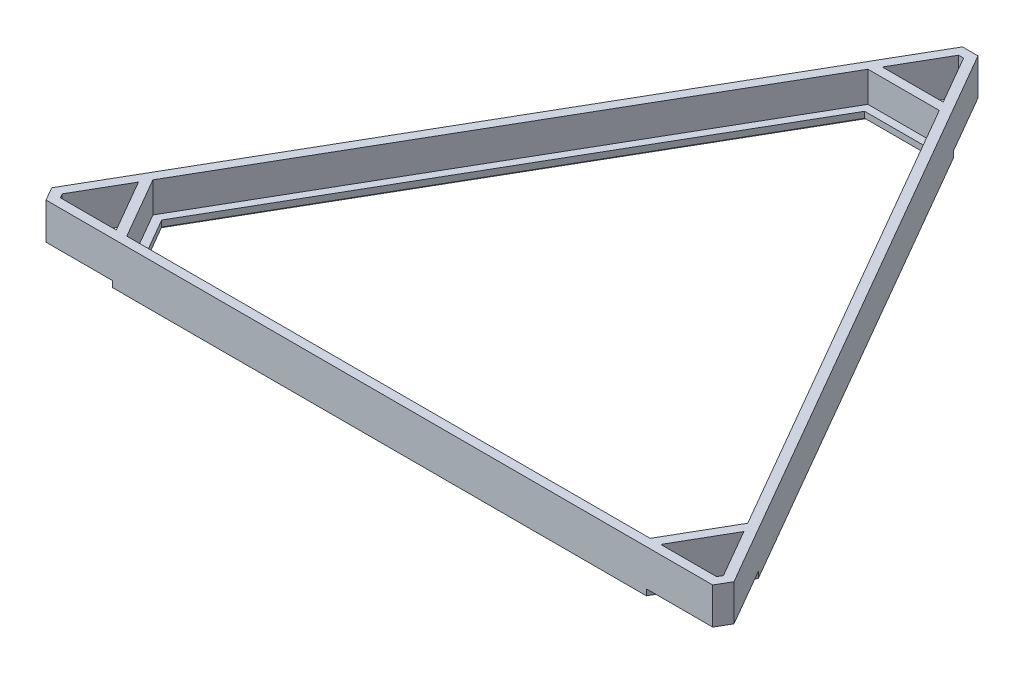
SolidWorks part; units mm, degrees
ref_plane "Front Plane" through (0, 0, 0) normal (0, 0, 1) x (1, 0, 0)
ref_plane "Top Plane" through (0, 0, 0) normal (0, 1, 0) x (1, 0, 0)
ref_plane "Right Plane" through (0, 0, 0) normal (1, 0, 0) x (0, 0, -1)
sketch "Sketch1" plane through (0, 0, 0) normal (0, 1, 0) x (1, 0, 0)
  line L17 (-4, 192.2576) -> (111, -6.9282) construction
  line L24 (4, 192.2576) -> (-111, -6.9282) construction
  line L25 (-115, 0) -> (115, 0) construction
  line L26 (0, -4.4282) -> (0, -1.4282) construction
  line L27 (-113, -3.4641) -> (-107, 0) construction
  line L28 (0, 192.2576) -> (0, 185.3294) construction
  line L29 (113, -3.4641) -> (107, 0) construction
  line L31 (-107.8246, -1.4282) -> (-108.6491, 0)
  line L39 (109.5566, -4.4282) -> (-109.5566, -4.4282)
  line L40 (-0.8246, 186.7576) -> (0.8246, 186.7576)
  line L41 (-109.5566, -4.4282) -> (-112.1132, 0)
  line L42 (-2.5566, 189.7576) -> (-112.1132, 0)
  line L43 (109.5566, -4.4282) -> (112.1132, 0)
  line L44 (-2.5566, 189.7576) -> (2.5566, 189.7576)
  line L45 (2.5566, 189.7576) -> (112.1132, 0)
  line L47 (108.6491, 0) -> (107.8246, -1.4282)
  line L50 (-99.4737, 15.8923) -> (-89.4737, -1.4282)
  line L51 (-107.8246, -1.4282) -> (-89.4737, -1.4282)
  line L52 (-99.4737, 15.8923) -> (-108.6491, 0)
  line L54 (89.4737, -1.4282) -> (107.8246, -1.4282)
  line L56 (89.4737, -1.4282) -> (99.4737, 15.8923)
  line L57 (99.4737, 15.8923) -> (108.6491, 0)
  line L58 (0, -1.4282) -> (0, 1.0718) construction
  line L59 (54.7369, 93.3788) -> (52.5718, 92.1288) construction
  line L62 (-10, 170.8653) -> (10, 170.8653)
  line L63 (-10, 170.8653) -> (-0.8246, 186.7576)
  line L64 (0.8246, 186.7576) -> (10, 170.8653)
  line L65 (94.4737, 7.2321) -> (91.8756, 8.7321) construction
  line L66 (-11.7321, 167.8653) -> (11.7321, 167.8653)
  line L67 (97.7417, 18.8923) -> (86.0096, -1.4282)
  line L68 (97.7417, 18.8923) -> (11.7321, 167.8653)
  line L69 (-54.7369, 93.3788) -> (-52.5718, 92.1288) construction
  line L70 (-84.5662, 1.0718) -> (84.5662, 1.0718)
  line L71 (-94.4737, 7.2321) -> (-91.8756, 8.7321) construction
  line L72 (-97.7417, 18.8923) -> (-86.0096, -1.4282)
  line L73 (-86.0096, -1.4282) -> (86.0096, -1.4282)
  line L74 (-97.7417, 18.8923) -> (-11.7321, 167.8653)
  line L75 (94.8549, 18.8923) -> (10.2887, 165.3653)
  line L76 (-10.2887, 165.3653) -> (-94.8549, 18.8923)
  line L77 (-91.8756, 8.7321) -> (-89.7106, 9.9821) construction
  line L78 (-94.8549, 18.8923) -> (-84.5662, 1.0718)
  line L79 (91.8756, 8.7321) -> (89.7106, 9.9821) construction
  line L80 (94.8549, 18.8923) -> (84.5662, 1.0718)
  line L81 (0, 167.8653) -> (0, 165.3653) construction
  line L82 (-10.2887, 165.3653) -> (10.2887, 165.3653)
  point P18 (0, -1.4282)
  point P41 (0, 167.8653)
  point P44 (91.8756, 8.7321)
  point P51 (-91.8756, 8.7321)
  point P55 (0, 1.0718)
  point P57 (-52.5718, 92.1288)
  point P61 (52.5718, 92.1288)
  point P65 (-89.7106, 9.9821)
  point P69 (89.7106, 9.9821)
  point P74 (0, 165.3653)
  dimension "D1" = 8
  dimension "D2" = 8
  dimension "D3" = 8
  dimension "D4" = 230
  dimension "D5" = 230
  dimension "D6" = 230
  dimension "D7" = 3
  dimension "D8" = 3
  dimension "D9" = 3
  dimension "D10" = 2.5
  dimension "D11" = 2.5
  dimension "D12" = 2.5
  dimension "D13" = 2.5
  dimension "D14" = 2.5
  dimension "D15" = 2.5
extrude "Boss-Extrude1" add sketch "Sketch1" along normal blind 12 contours L45 L43 L39 L41 L42 L44 | L74 L66 L68 L67 L73 L72 | L52 L31 L51 L50 | L57 L47 L54 L56 | L64 L62 L63 L40
extrude "Boss-Extrude2" add sketch "Sketch1<4>" along normal blind 2 contours L74 L72 L73 L67 L68 L66 L76 L82 L75 L80 L70 L78 region at (0, 0, -167.6067)
sketch "Sketch1<4>" plane through (0, 0, 0) normal (0, 1, 0) x (1, 0, 0) same geometry as "Sketch1"
sketch "Sketch2" plane through (0, 0, 0) normal (0, -1, 0) x (1, 0, 0)
  line L24 (-2.5566, -189.7576) -> (-112.1132, 0) construction
  line L25 (109.5566, 4.4282) -> (-109.5566, 4.4282) construction
  line L27 (2.5566, -189.7576) -> (112.1132, 0) construction
  line L33 (-89.4737, 1.4282) -> (-101.2058, -18.8923) construction
  line L34 (-89.4737, 1.4282) -> (-87.7417, 4.4282) construction
  line L35 (-11.7321, -167.8653) -> (11.7321, -167.8653)
  line L36 (89.4737, 1.4282) -> (87.7417, 4.4282) construction
  line L37 (99.4737, -15.8923) -> (101.2058, -18.8923) construction
  line L38 (86.0096, 1.4282) -> (97.7417, -18.8923)
  line L40 (101.2058, -18.8923) -> (87.7417, 4.4282)
  line L42 (-10, -170.8653) -> (-13.4641, -170.8653) construction
  line L43 (10, -170.8653) -> (13.4641, -170.8653) construction
  line L44 (87.7417, 4.4282) -> (-87.7417, 4.4282)
  line L45 (-97.7417, -18.8923) -> (-86.0096, 1.4282)
  line L46 (57.3349, -94.8788) -> (54.7369, -93.3788) construction
  line L47 (0, 4.4282) -> (0, 1.4282) construction
  line L48 (-87.7417, 4.4282) -> (-101.2058, -18.8923)
  line L49 (11.7321, -167.8653) -> (97.7417, -18.8923)
  line L50 (-86.0096, 1.4282) -> (86.0096, 1.4282)
  line L51 (-57.3349, -94.8788) -> (-54.7369, -93.3788) construction
  line L52 (-11.7321, -167.8653) -> (-97.7417, -18.8923)
  line L53 (-101.2058, -18.8923) -> (-13.4641, -170.8653)
  line L54 (-13.4641, -170.8653) -> (13.4641, -170.8653)
  line L55 (13.4641, -170.8653) -> (101.2058, -18.8923)
  point P66 (0, -167.8653)
  point P68 (-91.8756, -8.7321)
  point P72 (54.7369, -93.3788)
  point P75 (0, 1.4282)
  point P80 (-54.7369, -93.3788)
  dimension "D4" = 3
  dimension "D5" = 3
  dimension "D6" = 3
extrude "Boss-Extrude3" add sketch "Sketch2" along normal blind 2
